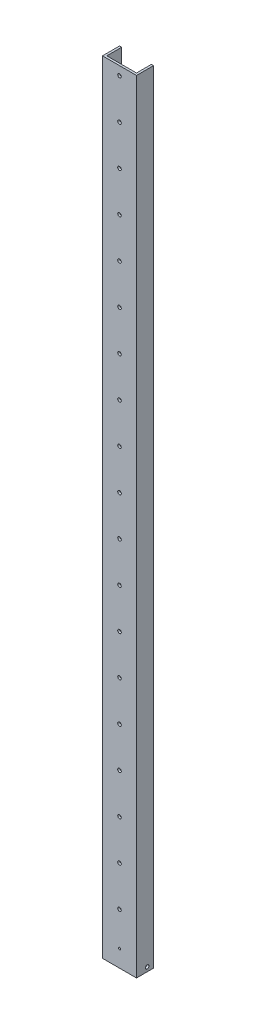
SolidWorks part; units mm, degrees
ref_plane "Front" through (0, 0, 0) normal (0, 0, 1) x (1, 0, 0)
ref_plane "Top" through (0, 0, 0) normal (0, 1, 0) x (1, 0, 0)
ref_plane "Right" through (0, 0, 0) normal (1, 0, 0) x (0, 0, -1)
sketch "Sketch1" plane through (0, 0, 0) normal (0, 1, 0) x (1, 0, 0)
  line L0 (3.175, 3.175) -> (3.175, 25.4)
  line L1 (0, 0) -> (50.8, 0)
  line L2 (0, 0) -> (0, 25.4)
  line L4 (50.8, 0) -> (50.8, 25.4)
  line L5 (3.175, 3.175) -> (47.625, 3.175)
  line L6 (47.625, 3.175) -> (47.625, 25.4)
  line L7 (0, 25.4) -> (3.175, 25.4)
  line L8 (50.8, 25.4) -> (47.625, 25.4)
  dimension "D1" = 25.4
  dimension "D2" = 50.8
  dimension "D3" = 3.175
extrude "Boss-Extrude1" add sketch "Sketch1" along normal blind 1168.4
sketch "Sketch2" plane through (0, 0, 0) normal (0, 0, 1) x (1, 0, 0)
  line L0 (25.4, 0) -> (25.4, 76.2) construction
  line L1 (0, 0) -> (50.8, 0) construction
  circle A0 centre (25.4, 76.2) radius 2.667
  circle A1 centre (25.4, 136.144) radius 2.667
  circle A2 centre (25.4, 196.088) radius 2.667
  circle A3 centre (25.4, 256.032) radius 2.667
  circle A4 centre (25.4, 315.976) radius 2.667
  circle A5 centre (25.4, 375.92) radius 2.667
  circle A6 centre (25.4, 435.864) radius 2.667
  circle A7 centre (25.4, 495.808) radius 2.667
  circle A8 centre (25.4, 555.752) radius 2.667
  circle A11 centre (25.4, 615.696) radius 2.667
  circle A12 centre (25.4, 675.64) radius 2.667
  circle A13 centre (25.4, 735.584) radius 2.667
  circle A14 centre (25.4, 795.528) radius 2.667
  circle A15 centre (25.4, 855.472) radius 2.667
  circle A16 centre (25.4, 915.416) radius 2.667
  circle A17 centre (25.4, 975.36) radius 2.667
  circle A18 centre (25.4, 1035.304) radius 2.667
  circle A19 centre (25.4, 1095.248) radius 2.667
  circle A20 centre (25.4, 1155.192) radius 2.667
  dimension "D2" = 5.334
  dimension "D1" = 76.2
  dimension "D3" = 19
extrude "Igus_Holes" cut sketch "Sketch2" against normal up to next
sketch "Sketch3" plane through (0, 0, -3.175) normal (0, 0, -1) x (-1, 0, 0)
  line L0 (-25.4, 0) -> (-25.4, 25.4) construction
  line L1 (-47.625, 0) -> (-3.175, 0) construction
  circle A0 centre (-25.4, 25.4) radius 1.5875
  dimension "D2" = 3.175
  dimension "D1" = 25.4
extrude "Cut-Extrude2" cut sketch "Sketch3" against normal up to next
sketch "Sketch4" plane through (0, 0, 0) normal (-1, 0, 0) x (0, 0, 1)
  line L0 (-15.875, 0) -> (-15.875, 6.35) construction
  line L2 (-25.4, 0) -> (0, 0) construction
  line L3 (-15.875, 6.35) -> (-25.4, 6.35) construction
  line L4 (-25.4, 1168.4) -> (-25.4, 0) construction
  circle A0 centre (-15.875, 6.35) radius 2.667
  dimension "D2" = 5.334
  dimension "D1" = 6.35
  dimension "D3" = 9.525
extrude "Cut-Extrude3" cut sketch "Sketch4" against normal through all
ref_plane "Mid_Plane" through (25.4, 0, 0) normal (1, 0, 0) x (0, 0, -1)
